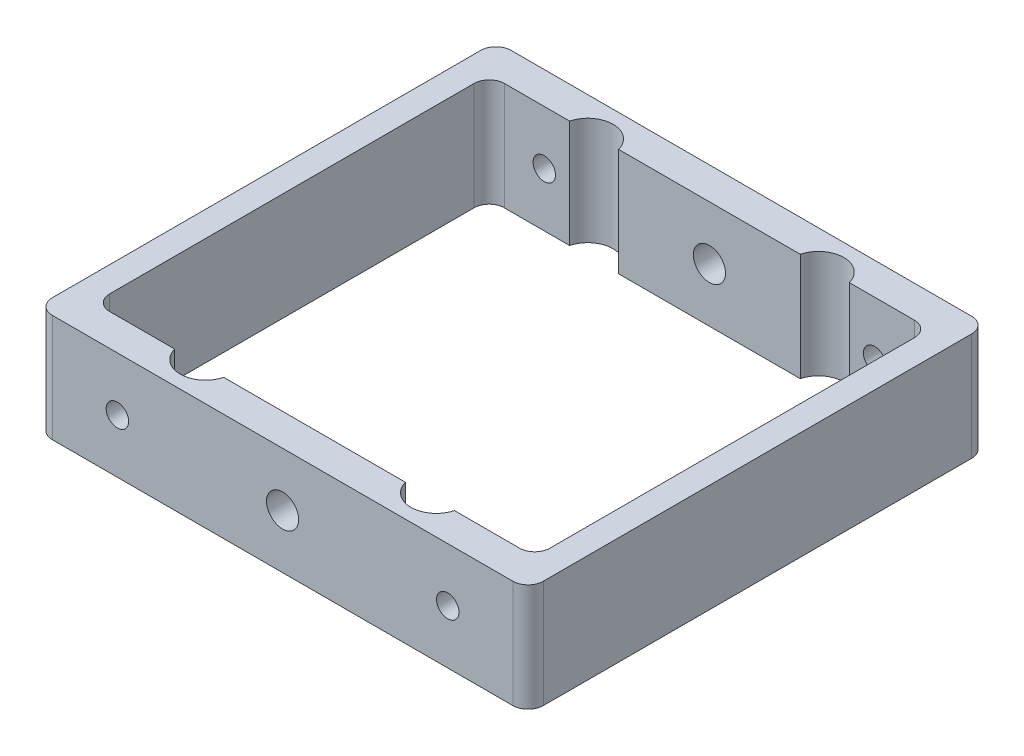
SolidWorks part; units mm, degrees
ref_plane "Front Plane" through (0, 0, 0) normal (0, 0, 1) x (1, 0, 0)
ref_plane "Top Plane" through (0, 0, 0) normal (0, 1, 0) x (1, 0, 0)
ref_plane "Right Plane" through (0, 0, 0) normal (1, 0, 0) x (0, 0, -1)
sketch "Sketch1" plane through (0, 0, 0) normal (0, 1, 0) x (1, 0, 0)
  line L1 (0, 0) -> (60, 0)
  line L2 (0, 0) -> (0, -6.32)
  line L3 (0, -6.32) -> (60, -6.32)
  line L4 (60, 0) -> (60, -6.32)
  dimension "D1" = 60
  dimension "D2" = 6.32
extrude "Boss-Extrude1" add sketch "Sketch1" along normal mid plane 21.28
sketch "Sketch2" plane through (0, 10.64, 0) normal (0, 1, 0) x (1, 0, 0)
  line L0 (0, 0) -> (0, -6.32) construction
  line L1 (0, -6.32) -> (60, -6.32) construction
  line L2 (60, -6.32) -> (60, 0) construction
  circle A0 centre (7.21, 1.25) radius 5
  circle A1 centre (52.79, 1.25) radius 5
  dimension "D1" = 7.21
  dimension "D3" = 7.21
  dimension "D2" = 7.57
  dimension "D4" = 7.57
extrude "Cut-Extrude1" cut sketch "Sketch2" against normal through all
sketch "Sketch3" plane through (60, 0, 0) normal (1, 0, 0) x (0, 0, -1)
  line L1 (-6.32, 10.64) -> (0, 10.64)
  line L2 (-6.32, 10.64) -> (-6.32, -10.64)
  line L3 (-6.32, -10.64) -> (0, -10.64)
  line L4 (0, 10.64) -> (0, -10.64)
extrude "Boss-Extrude2" add sketch "Sketch3" along normal blind 18.5
sketch "Sketch4" plane through (0, 0, 0) normal (-1, 0, 0) x (0, 0, 1)
  line L1 (0, 10.64) -> (6.32, 10.64)
  line L2 (0, 10.64) -> (0, -10.64)
  line L3 (0, -10.64) -> (6.32, -10.64)
  line L4 (6.32, 10.64) -> (6.32, -10.64)
extrude "Boss-Extrude3" add sketch "Sketch4" along normal blind 18.5
sketch "Sketch5" plane through (0, 0, 0) normal (0, 0, -1) x (-1, 0, 0)
  line L5 (-2.3688, -10.64) -> (18.5, -10.64) construction
  line L6 (18.5, 10.64) -> (13.5, 10.64)
  line L7 (18.5, 10.64) -> (18.5, -10.64)
  line L8 (18.5, -10.64) -> (13.5, -10.64)
  line L9 (13.5, 10.64) -> (13.5, -10.64)
  dimension "D1" = 5
extrude "Boss-Extrude6" add sketch "Sketch5" along normal blind 84.33
sketch "Sketch6" plane through (0, 0, 0) normal (0, 0, -1) x (-1, 0, 0)
  line L1 (-78.5, 10.64) -> (-73.5, 10.64)
  line L2 (-78.5, 10.64) -> (-78.5, -10.652)
  line L3 (-78.5, -10.652) -> (-73.5, -10.652)
  line L4 (-73.5, 10.64) -> (-73.5, -10.652)
  dimension "D1" = 5
extrude "Boss-Extrude7" add sketch "Sketch6" along normal blind 84.33
sketch "Sketch7" plane through (73.5, 0, 0) normal (-1, 0, 0) x (0, 0, 1)
  line L0 (-84.33, -10.652) -> (0, -10.652) construction
  line L1 (-84.33, 10.64) -> (-78.01, 10.64)
  line L2 (-84.33, 10.64) -> (-84.33, -10.652)
  line L3 (-84.33, -10.652) -> (-78.01, -10.652)
  line L4 (-78.01, 10.64) -> (-78.01, -10.652)
  dimension "D1" = 6.32
extrude "Boss-Extrude8" add sketch "Sketch7" along normal through all
sketch "Sketch9" plane through (0, 10.64, 0) normal (0, 1, 0) x (1, 0, 0)
  line L0 (-18.5, 84.33) -> (78.5, 84.33) construction
  circle A0 centre (7.21, 76.76) radius 5
  circle A1 centre (52.79, 76.76) radius 5
  dimension "D1" = 7.57
  dimension "D2" = 7.57
  dimension "D3" = 10
extrude "Cut-Extrude2" cut sketch "Sketch9" against normal through all
sketch "Sketch10" plane through (0, 0, -84.33) normal (0, 0, -1) x (-1, 0, 0)
  line L1 (-78.5, -10.64) -> (18.5, -10.64) construction
  line L2 (-30, -10.64) -> (-30, 10.64) construction
  line L3 (18.5, 10.64) -> (-78.5, 10.64) construction
  circle A0 centre (-62.6312, 0.005) radius 2.22
  circle A1 centre (2.6312, 0.005) radius 2.22
  dimension "D1" = 5
  dimension "D2" = 10.645
extrude "Cut-Extrude3" cut sketch "Sketch10" against normal through all
fillet "Fillet1" radius 3 8 edges at (-18.5, 0, 6.32) (78.5, 0, 6.32) (78.5, -0.006, -84.33) (-18.5, -0.006, -84.33) (-13.5, 0, -78.01) (-13.5, 0, 0) (73.5, -0.006, -78.01) (73.5, 0, 0)
sketch "Sketch13" plane through (0, 0, -84.33) normal (0, 0, -1) x (-1, 0, 0)
  line L1 (-75.5, 10.64) -> (-75.5, -10.652) construction
  line L2 (-75.5, -10.64) -> (15.5, -10.64) construction
  circle A0 centre (-30, 0.005) radius 3.175
  dimension "D1" = 45.5
  dimension "D3" = 6.35
  dimension "D2" = 10.645
extrude "Cut-Extrude4" cut sketch "Sketch13" against normal through all
sketch "Sketch16" plane through (0, -10.652, 0) normal (0, -1, 0) x (1, 0, 0)
  line L6 (75.5, -84.33) -> (-15.5, -84.33) construction
  line L7 (25.5729, -84.33) -> (12.6189, -84.33)
  line L8 (25.5729, -84.33) -> (25.5729, -78.01)
  line L9 (25.5729, -78.01) -> (12.6189, -78.01)
  line L10 (12.6189, -84.33) -> (12.6189, -78.01)
  line L11 (12.0512, -78.01) -> (47.9488, -78.01) construction
  dimension "D1" = 12.954
extrude "Cut-Extrude6" [suppressed] cut sketch "Sketch16" against normal mid plane 25.4
